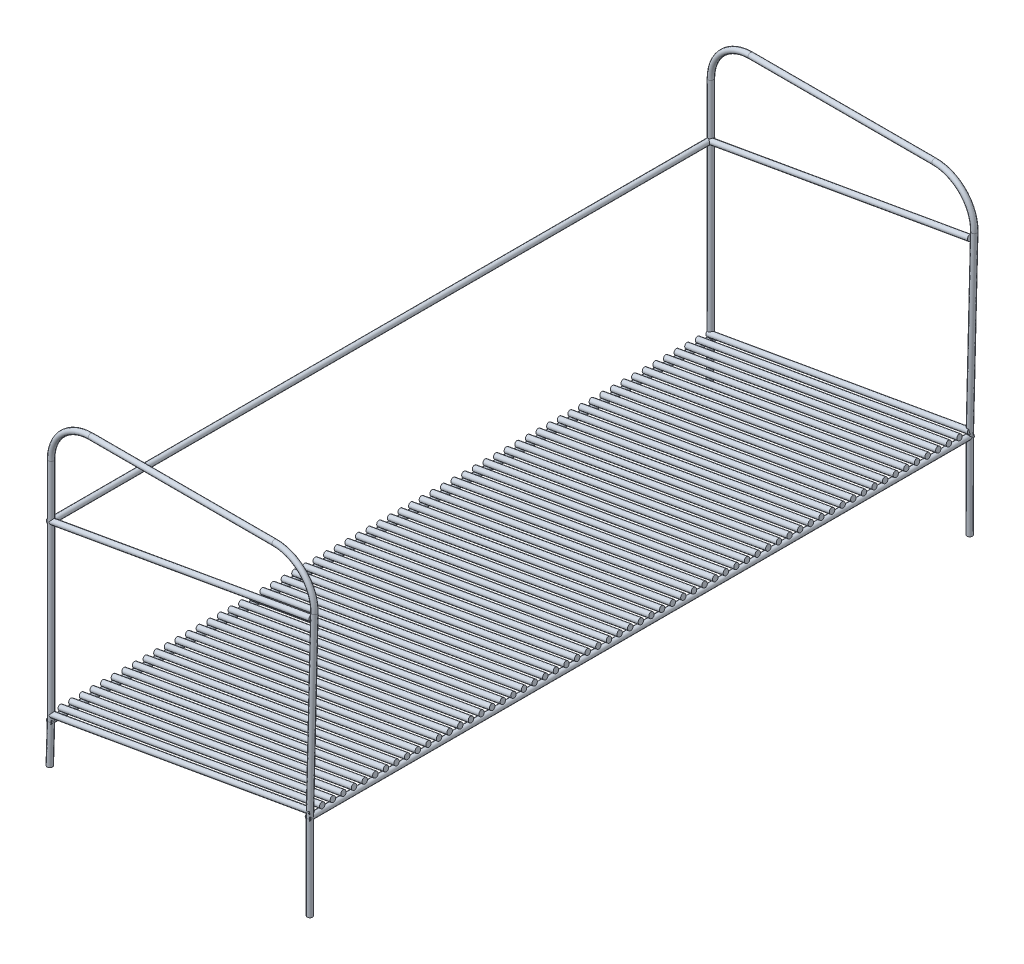
SolidWorks part; units mm, degrees
ref_plane "Front Plane" through (0, 0, 0) normal (0, 0, 1) x (1, 0, 0)
ref_plane "Top Plane" through (0, 0, 0) normal (0, 1, 0) x (1, 0, 0)
ref_plane "Right Plane" through (0, 0, 0) normal (1, 0, 0) x (0, 0, -1)
sketch "Esquisse1" plane through (0, 0, 0) normal (0, 0, 1) x (1, 0, 0)
  circle A0 centre (0, 0) radius 2
extrude "Boss.-Extru.1" add sketch "Esquisse1" along normal blind 500
ref_plane "right-plane" through (0, 0, 0) normal (1, 0, 0) x (0, 0, -1)
ref_plane "top-plane" through (0, 0, 0) normal (0, 1, 0) x (1, 0, 0)
ref_plane "front-plane" through (0, 0, 0) normal (0, 0, 1) x (1, 0, 0)
ref_axis "Axe1" through (0, 0, 500) along (0, 0, -1)
ref_plane "plan support" through (0, 0, 0) normal (0.9848, 0.1736, 0) x (0, 0, -1)
sketch "Esquisse4" plane through (0, 0, 100.428) normal (0.9848, 0.1736, 0) x (0, 0, -1)
  circle A0 centre (-398.056, 4.0014) radius 2
extrude "Boss.-Extru.3" add sketch "Esquisse4" along normal blind 200 separate body
pattern_linear "Répétition linéaire2" count 62 spacing 8 along (0, 0, -1) of "Boss.-Extru.3"
sketch "Esquisse5" plane through (-0.1003, -3.7689, 0) normal (0, 0, 1) x (1, 0, 0)
  line L1 (-0.2472, 5.7399) -> (196.7143, 40.4695) construction
  circle A0 centre (195.0617, 38.1473) radius 2
  dimension "D1" = 4
extrude "Boss.-Extru.4" add sketch "Esquisse5" along normal blind 500 separate body
ref_plane "base" through (0, -30, 0) normal (0, 1, 0) x (1, 0, 0)
ref_plane "droite" through (0, 0, -2) normal (0, 0, 1) x (1, 0, 0)
ref_axis "Axe2" through (206.9095, -30, 0) along (-1, 0, 0)
sketch "Esquisse29" plane through (0, 0, 0) normal (0, 0, 1) x (1, 0, 0)
  line L0 (-0.9802, -30) -> (0, 0)
  line L1 (109.4288, -30) -> (-109.4288, -30) construction
  line L2 (0, 0) -> (0, 170.2033)
  line L3 (0, -6.4903) -> (0, 6.4903) construction
  line L4 (30, 200.2033) -> (168.3684, 200.2033)
  line L5 (198.3589, 169.4489) -> (194.9614, 34.3784)
  line L6 (194.9614, 34.3784) -> (194.9614, -30)
  arc A0 (0, 170.2033) -> (30, 200.2033) centre (30, 170.2033) cw
  arc A1 (168.3684, 200.2033) -> (198.3589, 169.4489) centre (168.3684, 170.2033) cw
  point P15 (0, 200.2033)
  dimension "D1" = 30
sketch "Esquisse30" plane through (0, -30, 0) normal (0, 1, 0) x (1, 0, 0)
  circle A0 centre (194.9614, -1.4922) radius 2
sweep "Balayage8" add profiles "Esquisse30" path "Esquisse29"
pattern_linear "Répétition linéaire3" count 2 spacing 497 along (0, 0, 1) of "Balayage8"
pattern_linear "Répétition linéaire4" count 2 spacing 130 along (0, 1, 0) of "Boss.-Extru.1"
pattern_linear "Répétition linéaire10" count 2 spacing 496 along (0, 0, -1) count 2 spacing 126 along (0, 1, 0) of "Boss.-Extru.3"
